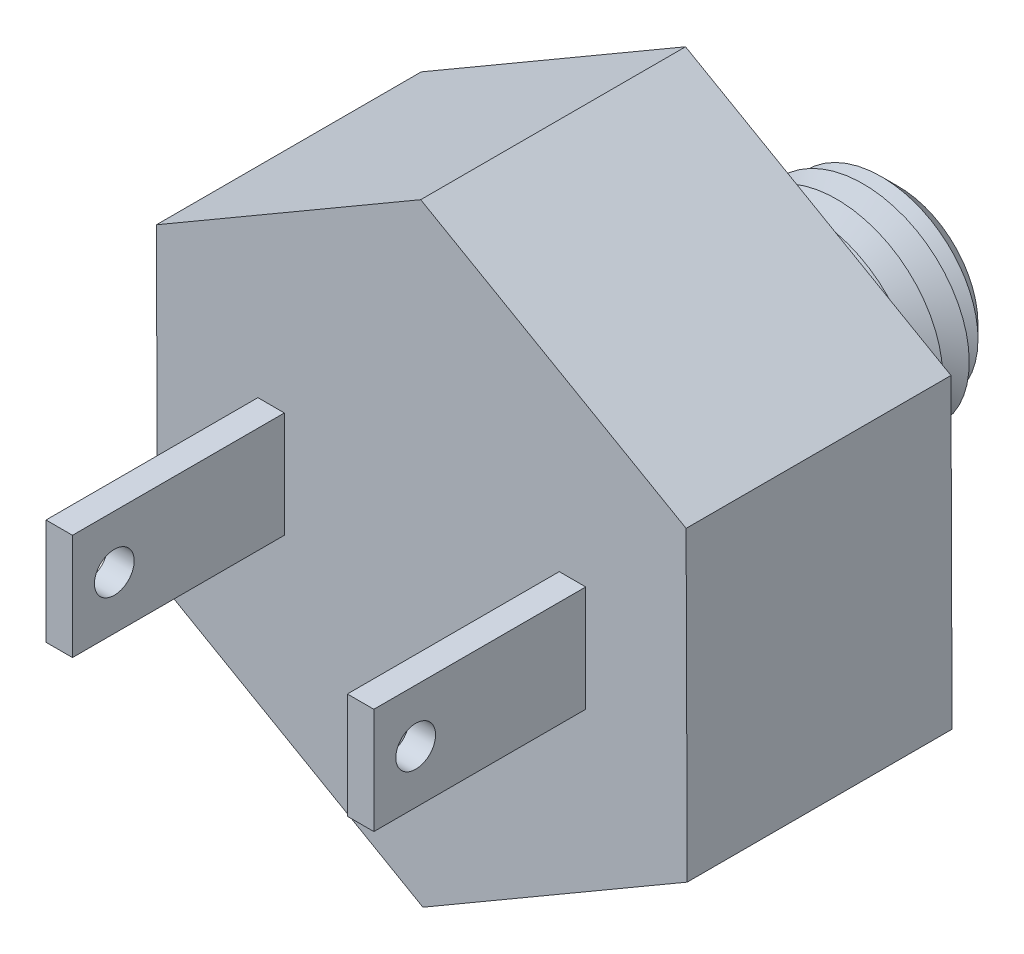
SolidWorks part; units mm, degrees
ref_plane "Plano frontal" through (0, 0, 0) normal (0, 0, 1) x (1, 0, 0)
ref_plane "Plano superior" through (0, 0, 0) normal (0, 1, 0) x (1, 0, 0)
ref_plane "Plano direito" through (0, 0, 0) normal (1, 0, 0) x (0, 0, -1)
sketch "Esboço1" plane through (0, 0, 0) normal (0, 0, 1) x (1, 0, 0)
  line L1 (10.0209, -5.7371) -> (9.9789, 5.8098)
  line L2 (9.9789, 5.8098) -> (-0.042, 11.5469)
  line L3 (-0.042, 11.5469) -> (-10.0209, 5.7371)
  line L4 (-10.0209, 5.7371) -> (-9.9789, -5.8098)
  line L5 (-9.9789, -5.8098) -> (0.042, -11.5469)
  line L6 (0.042, -11.5469) -> (10.0209, -5.7371)
  circle A0 centre (0, 0) radius 10 construction
  dimension "D1" = 20
extrude "Ressalto-extrusão1" add sketch "Esboço1" along normal blind 10
sketch "Esboço2" plane through (0, 0, 0) normal (0, 0, 1) x (1, 0, 0)
  circle A0 centre (0, 0) radius 4
  dimension "D1" = 8
extrude "Ressalto-extrusão2" add sketch "Esboço2" against normal blind 8
chamfer "Chanfro1" distance 1 angle 45 1 edges at (4, 0, -8)
sketch "Esboço4" plane through (0, 0, -8) normal (0, 0, -1) x (-1, 0, 0)
  circle A0 centre (0, 0) radius 4
  dimension "D1" = 8
curve "Hélice/Espiral2" pitch 1 height 8 radius 4 centre (0, 0, -8) axis (0, 0, 1) start towards (0, 1, 0)
sketch "Esboço5" plane through (0, 0, 0) normal (1, 0, 0) x (0, 0, -1)
  line L10 (8, 3.05) -> (8.8227, 4.475)
  line L11 (8.8227, 4.475) -> (7.1773, 4.475)
  line L12 (7.1773, 4.475) -> (8, 3.05)
  circle A0 centre (8, 4) radius 0.475 construction
  point P1 (0, 0)
  point P2 (0, 0)
  dimension "D1" = 0.95
sweep "Varredura de corte8" cut profiles "Esboço5" path "Hélice/Espiral2" align with end faces yes
ref_plane "Plano1" through (0, 0, 10) normal (0, 0, 1) x (1, 0, 0)
sketch "Esboço12" plane through (0, 0, 10) normal (0, 0, 1) x (1, 0, 0)
  line L0 (-9.4877, 0) -> (10.8088, 0) construction
  line L1 (0, -7.9815) -> (0, 8.3444) construction
  line L2 (6.1893, -2) -> (5.1893, -2)
  line L3 (-6.1893, 2) -> (-5.1893, 2)
  line L4 (-6.1893, 2) -> (-6.1893, -2)
  line L5 (-6.1893, -2) -> (-5.1893, -2)
  line L6 (-5.1893, 2) -> (-5.1893, -2)
  line L7 (-6.1893, 2) -> (-5.1893, -2) construction
  line L8 (-6.1893, -2) -> (-5.1893, 2) construction
  line L9 (5.1893, 2) -> (5.1893, -2)
  line L10 (6.1893, 2) -> (5.1893, 2)
  line L11 (6.1893, 2) -> (6.1893, -2)
  point P5 (-5.6893, 0)
  dimension "D1" = 1
  dimension "D2" = 4
extrude "Ressalto-extrusão3" add sketch "Esboço12" along normal blind 8
sketch "Esboço13" plane through (-6.1893, 0, 0) normal (-1, 0, 0) x (0, 0, 1)
  circle A0 centre (16.4206, 0) radius 0.7507
extrude "Corte-extrusão1" cut sketch "Esboço13" against normal through all
